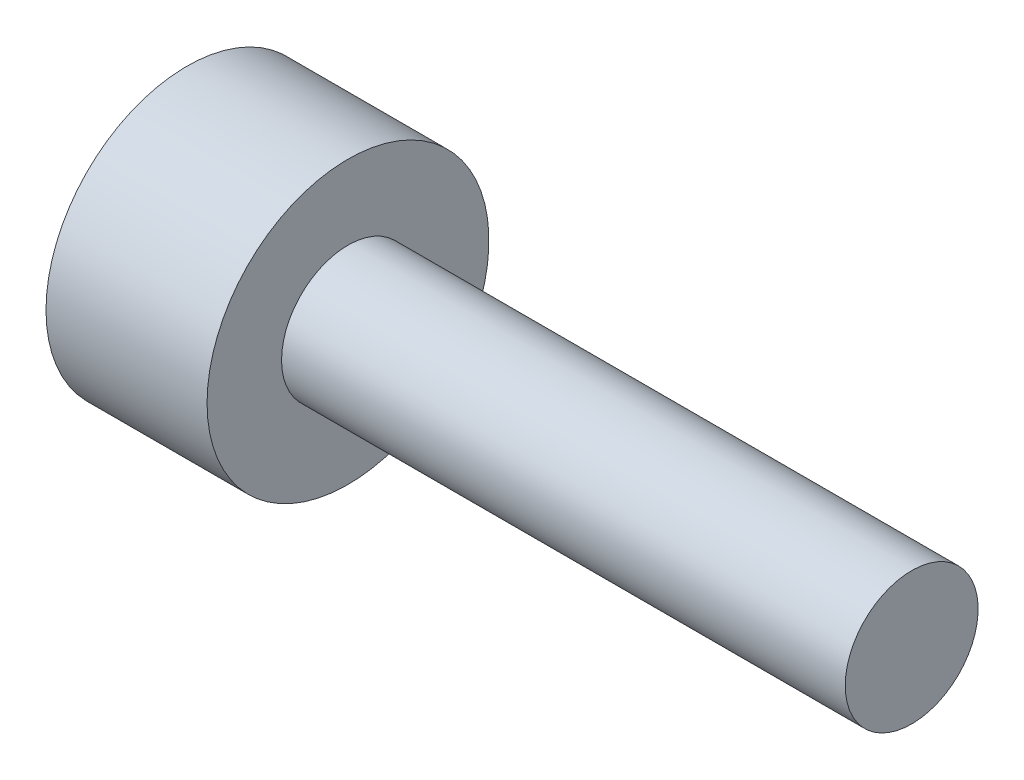
SolidWorks part; units mm, degrees
ref_plane "Front Plane" through (0, 0, 0) normal (0, 0, 1) x (1, 0, 0)
ref_plane "Top Plane" through (0, 0, 0) normal (0, 1, 0) x (1, 0, 0)
ref_plane "Right Plane" through (0, 0, 0) normal (1, 0, 0) x (0, 0, -1)
sketch "Screw Sketch" plane through (0, 0, 0) normal (0, 0, 1) x (1, 0, 0)
  line L0 (-1000, 0) -> (1000, 0) construction
  line L1 (-4, 0) -> (-4, 3.5)
  line L2 (-4, 3.5) -> (0, 3.5)
  line L3 (0, 3.5) -> (0, 1.65)
  line L4 (0, 1.65) -> (14, 1.65)
  line L5 (14, 1.65) -> (14, 0)
  line L6 (14, 0) -> (-4, 0)
revolve "Screw" add sketch "Screw Sketch" angle 360 about L0
ref_axis "Engine Axis" through (14.9, 0, 0) along (-1, 0, 0)
ref_plane "Head Top" through (-4, 0, 0) normal (1, 0, 0) x (0, 0, -1)
sketch "Socket Sketch" plane through (-4, 0, 0) normal (1, 0, 0) x (0, 0, -1)
  line L0 (1.7321, 0) -> (0.866, 1.5)
  line L1 (0.866, 1.5) -> (-0.866, 1.5)
  line L2 (-0.866, 1.5) -> (-1.7321, 0)
  line L3 (-1.7321, 0) -> (-0.866, -1.5)
  line L4 (-0.866, -1.5) -> (0.866, -1.5)
  line L5 (0.866, -1.5) -> (1.7321, 0)
extrude "Socket" cut sketch "Socket Sketch" along normal blind 2
